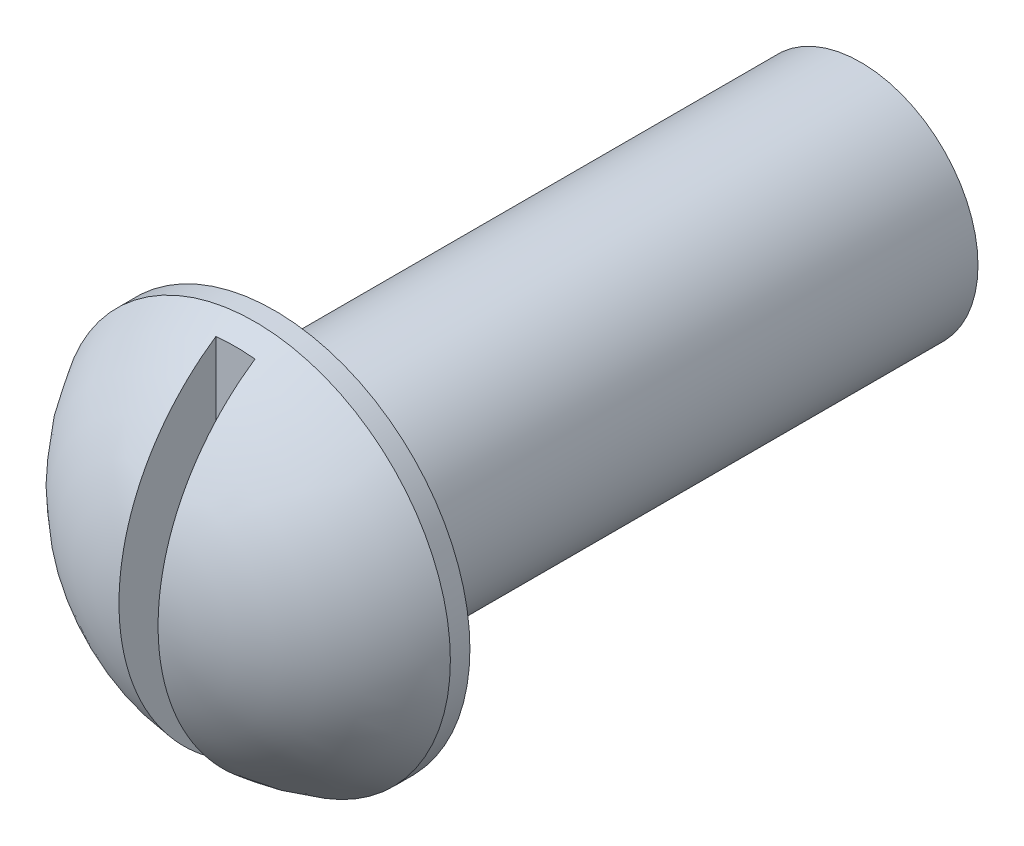
SolidWorks part; units mm, degrees
ref_plane "前视基准面" through (0, 0, 0) normal (0, 0, 1) x (1, 0, 0)
ref_plane "上视基准面" through (0, 0, 0) normal (0, 1, 0) x (1, 0, 0)
ref_plane "右视基准面" through (0, 0, 0) normal (1, 0, 0) x (0, 0, -1)
sketch "草图1" plane through (0, 0, 0) normal (0, 0, 1) x (1, 0, 0)
  line L0 (-0.45, -2.3832) -> (-1.05, -2.3832) construction
  circle A0 centre (-0.75, -2.3832) radius 0.3
extrude "凸台-拉伸1" add sketch "草图1" along normal blind 1.5
sketch "草图2" plane through (0, 0, 1.5) normal (0, 0, 1) x (1, 0, 0)
  circle A0 centre (-0.75, -2.3832) radius 0.5
  circle A1 centre (-0.75, -2.3832) radius 0.3
  circle A2 centre (-0.75, -2.3832) radius 0.3
  circle M2 centre (-0.75, -2.3832) radius 0.3
  dimension "D2" = 1
  dimension "D1" = 0
extrude "凸台-拉伸2" add sketch "草图2" along normal blind 0.05 contours M2 | A0 M2 region at (-1.2359, -2.3832, 1.5) region at (-0.75, -2.3832, 1.5)
dome "圆顶1" faces to dome 1 distance 0.3 reverse direction no elliptical dome no face at (-0.25, -2.3832, 1.55) parameters "D1"=0.3
ref_plane "基准面1" through (0, 0, 1.6) normal (0, 0, -1) x (-1, 0, 0)
sketch "草图3" plane through (0, 0, 1.6) normal (0, 0, -1) x (-1, 0, 0)
  line L0 (0.75, -2.3832) -> (0.75, -3.0108)
  line L1 (0.75, -2.3832) -> (0.75, -1.6242)
  line L2 (0.8, -2.3832) -> (0.8, -3.0108)
  line L3 (0.8, -2.3832) -> (0.8, -1.6242)
  line L4 (0.7, -2.3832) -> (0.7, -3.0108)
  line L5 (0.7, -2.3832) -> (0.7, -1.6242)
  line L6 (0.7, -1.6242) -> (0.8, -1.6242)
  line L7 (0.7, -3.0108) -> (0.8, -3.0108)
  dimension "D1" = 0.05
  dimension "D2" = 0.05
extrude "切除-拉伸1" cut sketch "草图3" against normal blind 3.12 contours L4 L7 L0 L1 L6 L5 | L3 L6 L5 L4 L7 L2 region at (-0.725, -2.3175, 1.6)
